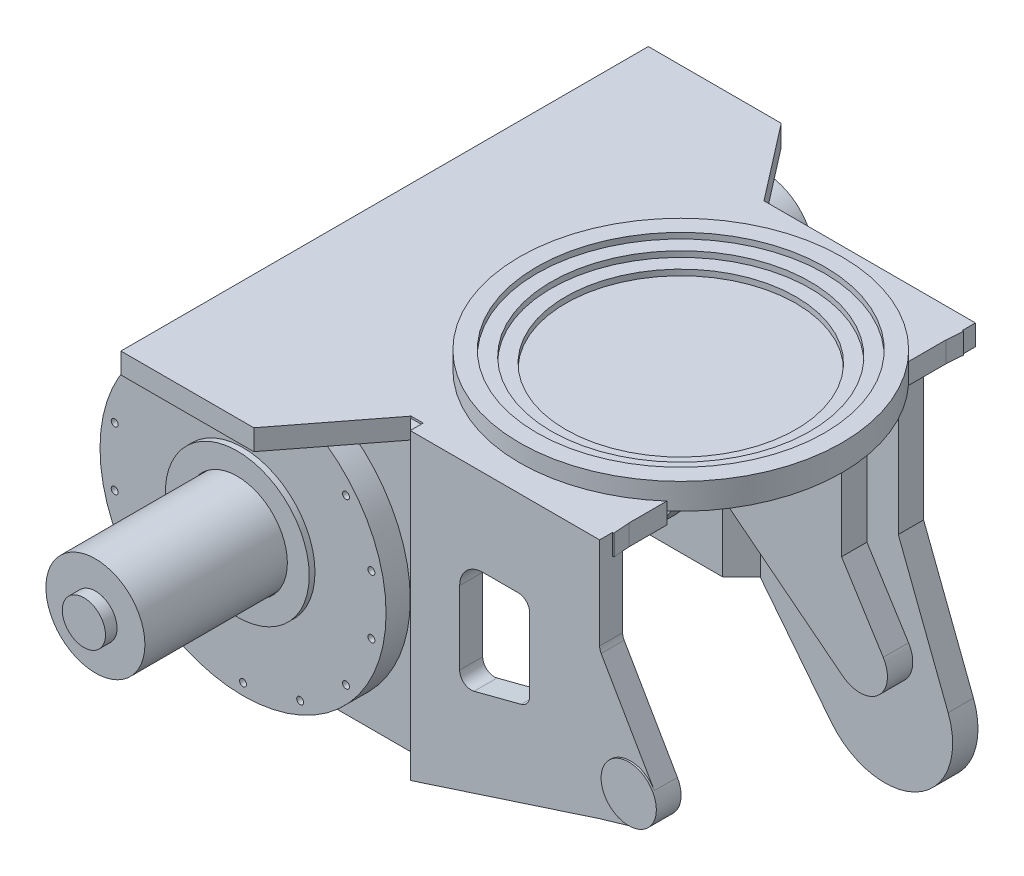
SolidWorks part; units mm, degrees
ref_plane "Front Plane" through (0, 0, 0) normal (0, 0, 1) x (1, 0, 0)
ref_plane "Top Plane" through (0, 0, 0) normal (0, 1, 0) x (1, 0, 0)
ref_plane "Right Plane" through (0, 0, 0) normal (1, 0, 0) x (0, 0, -1)
sketch "Sketch2" plane through (0, 0, 0) normal (0, 1, 0) x (1, 0, 0)
  line L1 (350, -275) -> (-350, -275)
  line L2 (350, -275) -> (350, 275)
  line L3 (350, 275) -> (-350, 275)
  line L4 (-350, -275) -> (-350, 275)
  line L5 (350, -275) -> (-350, 275) construction
  line L6 (350, 275) -> (-350, -275) construction
  point P0 (0, 0)
  dimension "D1" = 550
  dimension "D2" = 700
extrude "Boss-Extrude1" add sketch "Sketch2" along normal blind 2
sketch "Sketch3" plane through (0, 2, 0) normal (0, 1, 0) x (1, 0, 0)
  circle A0 centre (164.5242, 0) radius 280
  dimension "D1" = 560
extrude "Boss-Extrude3" add sketch "Sketch3" along normal blind 30 and the other way blind 15
sketch "Sketch7" plane through (0, 32, 0) normal (0, 1, 0) x (1, 0, 0)
  circle A0 centre (164.5242, 0) radius 250
extrude "Cut-Extrude2" cut sketch "Sketch7" against normal blind 10
sketch "Sketch9" plane through (0, 22, 0) normal (0, 1, 0) x (1, 0, 0)
  circle A0 centre (164.5242, 0) radius 225
extrude "Cut-Extrude3" cut sketch "Sketch9" against normal blind 10
sketch "Sketch10" plane through (0, 12, 0) normal (0, 1, 0) x (1, 0, 0)
  circle A0 centre (164.5242, 0) radius 200
extrude "Cut-Extrude4" cut sketch "Sketch10" against normal blind 10
sketch "Sketch12" plane through (0, 0, 0) normal (0, -1, 0) x (1, 0, 0)
  line L0 (-350, -275) -> (-350, -458.1483)
  line L1 (-350, -458.1483) -> (-119.077, -458.1483)
  line L2 (-119.077, -458.1483) -> (0, -303.9607)
  line L3 (352.1511, -303.9607) -> (0, -303.9607)
  line L4 (352.1511, -303.9607) -> (350, -275)
  line L5 (350, -275) -> (-350, -275)
  line L6 (-350, 275) -> (-350, 326.4525)
  line L7 (-350, 326.4525) -> (350, 326.4525)
  line L8 (350, 326.4525) -> (350, 275)
  line L9 (350, 275) -> (-350, 275)
extrude "Boss-Extrude7" add sketch "Sketch12" against normal blind 2
sketch "Sketch14" plane through (0, 2, 0) normal (0, 1, 0) x (1, 0, 0)
  line L0 (-350, 458.1483) -> (-350, -326.4525) construction
  line L1 (350, -326.4525) -> (-150, -326.4525)
  line L2 (350, -326.4525) -> (350, -286.4525)
  line L3 (350, -286.4525) -> (-150, -286.4525)
  line L4 (-150, -326.4525) -> (-150, -286.4525)
  dimension "D1" = 200
  dimension "D2" = 40
extrude "Boss-Extrude8" add sketch "Sketch14" against normal blind 582
sketch "Sketch16" plane through (0, 0, 326.4525) normal (0, 0, 1) x (1, 0, 0)
  line L0 (-150, -580) -> (350, -417.5402)
  line L1 (350, 2) -> (350, -580) construction
  line L2 (350, -417.5402) -> (350, -580)
  line L3 (350, -580) -> (-150, -580)
  line L4 (-150, -580) -> (-150, 0) construction
  dimension "D1" = 72
extrude "Cut-Extrude5" cut sketch "Sketch16" against normal blind 582
sketch "Sketch17" plane through (0, 0, 326.4525) normal (0, 0, 1) x (1, 0, 0)
  circle A0 centre (350, -417.5402) radius 5
sketch "Sketch19" plane through (0, 0, 326.4525) normal (0, 0, 1) x (1, 0, 0)
  line L1 (350, 2) -> (350, -417.5402) construction
  line L2 (350, -163) -> (475.6516, -380.635)
  line L3 (350, -417.5402) -> (475.6516, -380.635)
  line L4 (350, -417.5402) -> (350, -163)
extrude "Boss-Extrude9" add sketch "Sketch19" against normal up to surface (40 mm away) up to face at (100, -249.385, 286.4525)
sketch "Sketch20" plane through (0, 0, 326.4525) normal (0, 0, 1) x (1, 0, 0)
  line L0 (-150, -580) -> (21, -524.4387)
  line L1 (350, -417.5402) -> (-150, -580) construction
  line L2 (21, -524.4387) -> (21, 2)
  line L3 (350, 2) -> (-350, 2) construction
  line L5 (-150, 0) -> (-150, -580)
  line L8 (350, 2) -> (350, -163) construction
  line L9 (21, 2) -> (21, 86.1242)
  line L10 (21, 86.1242) -> (-150, 86.1242)
  line L11 (-150, 86.1242) -> (-150, 0)
  dimension "D1" = 329
extrude "Cut-Extrude9" cut sketch "Sketch20" against normal blind 40
sketch "Sketch21" plane through (0, 0, 326.4525) normal (0, 0, 1) x (1, 0, 0)
  line L0 (475.6516, -380.635) -> (350, -163) construction
  line L1 (350, -417.5402) -> (475.6516, -380.635) construction
  circle A0 centre (403.5663, -351.7796) radius 48
  dimension "D1" = 96
extrude "Boss-Extrude10" add sketch "Sketch21" along normal blind 3 and the other way up to surface (40 mm away) other way up to face at (261.2753, -247.6023, 286.4525)
sketch "Sketch22" plane through (0, 0, 326.4525) normal (0, 0, 1) x (1, 0, 0)
  line L2 (417.0931, -397.8342) -> (475.6516, -380.635)
  line L3 (475.6516, -380.635) -> (445.1356, -327.7796)
  line L4 (417.0931, -397.8342) -> (475.6516, -380.635)
  line L5 (475.6516, -380.635) -> (445.1356, -327.7796)
  arc A1 (417.0931, -397.8342) -> (445.1356, -327.7796) centre (403.5663, -351.7796) ccw
  arc A2 (417.0931, -397.8342) -> (445.1356, -327.7796) centre (403.5663, -351.7796) ccw
  dimension "D1" = 0
extrude "Cut-Extrude10" cut sketch "Sketch22" against normal blind 83
ref_plane "Plane2" through (0, -524.44, 0) normal (0, -1, 0) x (-1, 0, 0)
sketch "Sketch24" plane through (0, -524.44, 0) normal (0, -1, 0) x (-1, 0, 0)
  line L0 (-21, -286.4525) -> (14.3553, -251.0972)
  line L1 (14.3553, -251.0972) -> (431.5305, -251.0972)
  line L5 (-21, -326.4525) -> (-21, -286.4525)
  line L6 (-21, -326.4525) -> (22.5103, -282.9422)
  line L9 (22.5103, -282.9422) -> (431.5305, -282.9422)
  line L10 (150, -326.4525) -> (350, -326.4525) construction
  line L13 (431.5305, -282.9422) -> (431.5305, -251.0972)
  dimension "D1" = 50
  dimension "D2" = 135
extrude "Boss-Extrude13" add sketch "Sketch24" against normal blind 523
sketch "Sketch25" plane through (0, 0, 0) normal (0, -1, 0) x (1, 0, 0)
  line L1 (-150, 286.4525) -> (-350, 286.4525)
  line L2 (-150, 286.4525) -> (-150, 326.4525)
  line L3 (-150, 326.4525) -> (-350, 326.4525)
  line L4 (-350, 286.4525) -> (-350, 326.4525)
extrude "Cut-Extrude11" cut sketch "Sketch25" against normal blind 523
sketch "Sketch27" plane through (0, 0, 282.9422) normal (0, 0, 1) x (1, 0, 0)
  line L0 (-22.5103, -1.44) -> (-22.5103, -524.44) construction
  line L1 (-22.5103, -1.44) -> (-22.5103, -295.44)
  circle A0 centre (-271.0103, -295.44) radius 248.5
  line M2 (-431.5305, -524.44) -> (-22.5103, -524.44)
  line M5 (-431.5305, -1.44) -> (-431.5305, -524.44)
  dimension "D1" = 497
  dimension "D2" = 294
extrude "Boss-Extrude14" add sketch "Sketch27" against normal blind 73.85 and the other way blind 42 contours A0 M5 M2 | A0 M5 | A0 M2 region at (-243.9679, -291.8807, 282.9422) region at (-467.3178, -295.44, 282.9422) region at (-271.0103, -532.2668, 282.9422)
sketch "Sketch30" plane through (0, 0, 209.0922) normal (0, 0, -1) x (-1, 0, 0)
  circle A0 centre (271.0103, -295.44) radius 236.5
extrude "Boss-Extrude15" add sketch "Sketch30" along normal blind 16
sketch "Sketch31" plane through (0, 0, 193.0922) normal (0, 0, -1) x (-1, 0, 0)
  circle A0 centre (271.0103, -295.44) radius 197.5
extrude "Boss-Extrude16" add sketch "Sketch31" along normal blind 15
sketch "Sketch32" plane through (0, 0, 178.0922) normal (0, 0, -1) x (-1, 0, 0)
  circle A0 centre (271.0103, -295.44) radius 162.5
extrude "Boss-Extrude17" add sketch "Sketch32" along normal blind 7
sketch "Sketch33" plane through (0, 0, 171.0922) normal (0, 0, -1) x (-1, 0, 0)
  circle A0 centre (271.0103, -295.44) radius 137.5
extrude "Boss-Extrude18" add sketch "Sketch33" along normal blind 12
sketch "Sketch34" plane through (0, 0, 324.9422) normal (0, 0, 1) x (1, 0, 0)
  circle A0 centre (-271.0103, -295.44) radius 125
extrude "Boss-Extrude19" add sketch "Sketch34" along normal blind 10
sketch "Sketch35" plane through (0, 0, 334.9422) normal (0, 0, 1) x (1, 0, 0)
  circle A0 centre (-271.0103, -295.44) radius 87
extrude "Cut-Extrude12" cut sketch "Sketch35" against normal blind 50
sketch "Sketch36" plane through (0, 0, 284.9422) normal (0, 0, 1) x (1, 0, 0)
  circle A0 centre (-271.0103, -295.44) radius 86
extrude "Boss-Extrude20" add sketch "Sketch36" along normal blind 296.5
sketch "Sketch37" plane through (0, 0, 581.4422) normal (0, 0, 1) x (1, 0, 0)
  circle A0 centre (-271.0103, -295.44) radius 37.5
extrude "Boss-Extrude21" add sketch "Sketch37" along normal blind 20
fillet "Fillet1" radius 20 1 edges at (350, -163, 306.4525)
mirror "Mirror4" about plane through (0, 0, 0) normal (0, 0, 1) of "Boss-Extrude7", "Boss-Extrude10", "Boss-Extrude1", "Boss-Extrude9", "Cut-Extrude5", "Boss-Extrude8", "Boss-Extrude18", "Boss-Extrude17", "Boss-Extrude16", "Boss-Extrude15", "Boss-Extrude13", "Boss-Extrude14", "Boss-Extrude19", "Boss-Extrude21", "Boss-Extrude20"
sketch "Sketch40" plane through (0, 0, -286.4525) normal (0, 0, 1) x (1, 0, 0)
  line L12 (-150, 0) -> (-150, -78.3945)
  line L13 (-150, -512.4855) -> (-150, -580)
  line L14 (-150, -580) -> (20.9961, -524.44)
  line L15 (20.9961, -524.44) -> (-19, -524.44)
  line L16 (-19, -524.44) -> (-19, -1.44)
  line L17 (-19, -1.44) -> (21, -1.44)
  line L18 (21, -1.44) -> (21, -524.4387)
  line L19 (21, -524.4387) -> (350, -417.5402)
  line L20 (350, -417.5402) -> (475.6516, -380.635)
  line L21 (475.6516, -380.635) -> (350, -163)
  line L22 (350, -163) -> (350, 0)
  line L23 (350, 0) -> (-150, 0)
  line L24 (-150, 0) -> (-150, -78.3945)
  line L25 (-150, -512.4855) -> (-150, -580)
  line L26 (-150, -580) -> (20.9961, -524.44)
  line L27 (20.9961, -524.44) -> (-19, -524.44)
  line L28 (-19, -524.44) -> (-19, -1.44)
  line L29 (-19, -1.44) -> (21, -1.44)
  line L30 (21, -1.44) -> (21, -524.4387)
  line L31 (21, -524.4387) -> (350, -417.5402)
  line L32 (350, -417.5402) -> (475.6516, -380.635)
  line L33 (475.6516, -380.635) -> (350, -163)
  line L34 (350, -163) -> (350, 0)
  line L35 (350, 0) -> (-150, 0)
  arc A1 (-150, -512.4855) -> (-150, -78.3945) centre (-271.0103, -295.44) ccw
  arc A2 (-150, -512.4855) -> (-150, -78.3945) centre (-271.0103, -295.44) ccw
  dimension "D1" = 0
extrude "Cut-Extrude14" cut sketch "Sketch40" against normal blind 80
sketch "Sketch41" plane through (0, 0, -326.4525) normal (0, 0, -1) x (-1, 0, 0)
  line L0 (-21, -524.44) -> (-119.3307, -649.1719)
  line L2 (-338.0133, -541.9318) -> (-260, -339.44)
  line L3 (-260, -339.44) -> (-260, 2)
  line L4 (-350, 2) -> (17.3701, 2) construction
  line L5 (-260, 2) -> (-21, -1.44)
  line L6 (-21, -1.44) -> (-21, -524.44)
  line L7 (-21, -524.44) -> (-479.957, -524.44) construction
  line L8 (-119.3307, -649.1719) -> (-143.4961, -679.8256)
  line L9 (-338.0133, -541.9318) -> (-346.5828, -564.1748)
  arc A0 (-346.5828, -564.1748) -> (-143.4961, -679.8256) centre (-236.3045, -606.6613) ccw
  dimension "D1" = 239
  dimension "D2" = 158.83
  dimension "D3" = 217
  dimension "D4" = 158.93
  dimension "D5" = 141.75
  dimension "D6" = 185
extrude "Boss-Extrude22" add sketch "Sketch41" against normal blind 44
sketch "Sketch42" plane through (0, 0, -326.4525) normal (0, 0, -1) x (-1, 0, 0)
  circle A0 centre (-236.3045, -606.6613) radius 84
extrude "Boss-Extrude23" add sketch "Sketch42" along normal blind 5
sketch "Sketch43" plane through (0, 0, -331.4525) normal (0, 0, -1) x (-1, 0, 0)
  circle A0 centre (-236.3045, -606.6613) radius 56
extrude "Boss-Extrude24" add sketch "Sketch43" along normal blind 9
sketch "Sketch44" plane through (0, 0, -340.4525) normal (0, 0, -1) x (-1, 0, 0)
  circle A0 centre (-236.3045, -606.6613) radius 31
extrude "Boss-Extrude25" add sketch "Sketch44" along normal blind 12
sketch "Sketch45" plane through (0, 0, -352.4525) normal (0, 0, -1) x (-1, 0, 0)
  circle A0 centre (-236.3045, -606.6613) radius 27
extrude "Boss-Extrude26" add sketch "Sketch45" along normal blind 4
sketch "Sketch46" plane through (0, 0, -282.9422) normal (0, 0, -1) x (-1, 0, 0)
  line L0 (349.8838, -1.44) -> (431.5305, -102.5155)
  line L1 (22.5103, -1.44) -> (431.5305, -1.44) construction
  line L2 (431.5305, -1.44) -> (431.5305, -105.7415) construction
  line L3 (431.5305, -102.5155) -> (431.5305, -1.44)
  line L4 (431.5305, -1.44) -> (349.8838, -1.44)
extrude "Cut-Extrude18" cut sketch "Sketch46" against normal through all contours L4 L0 L3
sketch "Sketch50" plane through (-211.0253, 170.4617, 0) normal (-0.7779, 0.6284, 0) x (0, 0, 1)
  line L0 (282.9422, -350.9118) -> (-282.9422, -350.9118)
  line L1 (282.9422, -350.9118) -> (251.0972, -350.9118) construction
  line L2 (-282.9422, -350.9118) -> (-282.9422, -220.9794)
  line L3 (-282.9422, -220.9794) -> (282.9422, -220.9794)
  line L4 (282.9422, -220.9794) -> (282.9422, -350.9118)
extrude "Boss-Extrude28" add sketch "Sketch50" against normal blind 5
sketch "Sketch51" plane through (-211.0253, 170.4617, 0) normal (-0.7779, 0.6284, 0) x (0, 0, 1)
  line L0 (-251.0972, -350.9118) -> (251.0972, -350.9118) construction
  line L1 (122.2502, -350.9118) -> (42.4318, -350.9118)
  line L2 (122.2502, -350.9118) -> (122.2502, -302.3775)
  line L3 (122.2502, -302.3775) -> (42.4318, -302.3775)
  line L4 (42.4318, -350.9118) -> (42.4318, -302.3775)
extrude "Cut-Extrude19" cut sketch "Sketch51" against normal blind 5
sketch "Sketch52" plane through (-211.0253, 170.4617, 0) normal (-0.7779, 0.6284, 0) x (0, 0, 1)
  line L0 (-251.0972, -350.9118) -> (42.4318, -350.9118) construction
  line L1 (-127.4075, -350.9118) -> (-55.046, -350.9118)
  line L2 (-127.4075, -350.9118) -> (-127.4075, -302.3775)
  line L3 (-127.4075, -302.3775) -> (-55.046, -302.3775)
  line L4 (-55.046, -350.9118) -> (-55.046, -302.3775)
extrude "Cut-Extrude20" cut sketch "Sketch52" against normal blind 5
ref_plane "Plane3" through (0, 0, -116.4525) normal (0, 0, -1) x (-1, 0, 0)
sketch "Sketch55" plane through (0, 0, -116.4525) normal (0, 0, -1) x (-1, 0, 0)
  line L0 (-373.5582, -390.624) -> (-140.9519, -208.2316)
  line L1 (-443.8156, -327.3083) -> (-371.443, -212.1641)
  line L5 (-61.443, -93) -> (-140.9519, -208.2316)
  line L6 (-371.443, -212.1641) -> (-371.443, -13)
  line L7 (-444.5242, -13) -> (115.4758, -13) construction
  line L8 (-371.443, -13) -> (-61.443, -13)
  line L9 (-61.443, -13) -> (-61.443, -93)
  arc A0 (-443.8156, -327.3083) -> (-373.5582, -390.624) centre (-403.1765, -352.8516) ccw
  dimension "D1" = 310
  dimension "D2" = 80
  dimension "D3" = 199.1641
  dimension "D4" = 140
extrude "Boss-Extrude29" add sketch "Sketch55" against normal blind 44
sketch "Sketch57" plane through (0, 0, 326.4525) normal (0, 0, 1) x (1, 0, 0)
  line L0 (208.482, -148.32) -> (146.8301, -148.32)
  line L1 (106.8301, -188.32) -> (106.8301, -315.4783)
  line L2 (131.8586, -334.8359) -> (213.5105, -313.6251)
  line L3 (228.482, -294.2676) -> (228.482, -168.32)
  arc A0 (146.8301, -148.32) -> (106.8301, -188.32) centre (146.8301, -188.32) ccw
  arc A1 (208.482, -148.32) -> (228.482, -168.32) centre (208.482, -168.32) cw
  arc A2 (213.5105, -313.6251) -> (228.482, -294.2676) centre (208.482, -294.2676) ccw
  arc A3 (106.8301, -315.4783) -> (131.8586, -334.8359) centre (126.8301, -315.4783) ccw
  dimension "D1" = 40
  dimension "D2" = 20
extrude "Cut-Extrude21" cut sketch "Sketch57" against normal blind 84
sketch "Sketch58" plane through (0, 0, -326.4525) normal (0, 0, -1) x (-1, 0, 0)
  line L0 (-157.0738, -257.6457) -> (-37.7461, -163.6967)
  line L1 (-29.3553, -146.4112) -> (-29.3553, -68.0328)
  line L2 (-51.3553, -46.0328) -> (-162.2533, -46.0328)
  line L3 (-184.2533, -68.0328) -> (-184.2533, -262.0746)
  line L4 (-182.2533, -264.0746) -> (-175.6318, -264.0746)
  arc A0 (-157.0738, -257.6457) -> (-175.6318, -264.0746) centre (-175.6318, -234.0746) cw
  arc A1 (-184.2533, -262.0746) -> (-182.2533, -264.0746) centre (-182.2533, -262.0746) ccw
  arc A2 (-162.2533, -46.0328) -> (-184.2533, -68.0328) centre (-162.2533, -68.0328) ccw
  arc A3 (-29.3553, -68.0328) -> (-51.3553, -46.0328) centre (-51.3553, -68.0328) ccw
  arc A4 (-37.7461, -163.6967) -> (-29.3553, -146.4112) centre (-51.3553, -146.4112) ccw
  dimension "D1" = 30
  dimension "D2" = 2
  dimension "D3" = 22
extrude "Cut-Extrude22" cut sketch "Sketch58" against normal blind 84
sketch "Sketch59" plane through (0, 0, 0) normal (0, -1, 0) x (1, 0, 0)
  line L0 (-119.077, -458.1483) -> (-68.2236, -392.3004)
  line L1 (-119.077, -458.1483) -> (-17.3701, -326.4525) construction
  line L23 (121.0465, -282.4525) -> (260, -282.4525)
  line L24 (260, -282.4525) -> (260, -326.4525)
  line L25 (260, -326.4525) -> (350, -326.4525)
  line L26 (350, -326.4525) -> (350, -303.9607)
  line L27 (350, -303.9607) -> (352.1511, -303.9607)
  line L28 (352.1511, -303.9607) -> (350, -275)
  line L29 (350, -275) -> (350, -209.7587)
  line L30 (350, 209.7587) -> (350, 275)
  line L31 (350, 275) -> (352.1511, 303.9607)
  line L32 (352.1511, 303.9607) -> (350, 303.9607)
  line L33 (350, 303.9607) -> (350, 286.4525)
  line L34 (350, 286.4525) -> (21, 286.4525)
  line L35 (21, 286.4525) -> (21, 303.9607)
  line L36 (21, 303.9607) -> (0, 303.9607)
  line L37 (0, 303.9607) -> (-119.077, 458.1483)
  line L38 (-119.077, 458.1483) -> (-350, 458.1483)
  line L39 (-350, 458.1483) -> (-350, -458.1483)
  line L40 (-350, -458.1483) -> (-119.077, -458.1483)
  line L41 (-119.077, -458.1483) -> (-17.3701, -326.4525)
  line L42 (-17.3701, -326.4525) -> (121.0465, -326.4525)
  line L43 (121.0465, -326.4525) -> (121.0465, -282.4525)
  line L44 (121.0465, -282.4525) -> (260, -282.4525)
  line L45 (260, -282.4525) -> (260, -326.4525)
  line L46 (260, -326.4525) -> (350, -326.4525)
  line L47 (350, -326.4525) -> (350, -303.9607)
  line L48 (350, -303.9607) -> (352.1511, -303.9607)
  line L49 (352.1511, -303.9607) -> (350, -275)
  line L50 (350, -275) -> (350, -209.7587)
  line L51 (350, 209.7587) -> (350, 275)
  line L52 (350, 275) -> (352.1511, 303.9607)
  line L53 (352.1511, 303.9607) -> (350, 303.9607)
  line L54 (350, 303.9607) -> (350, 286.4525)
  line L55 (350, 286.4525) -> (21, 286.4525)
  line L56 (21, 286.4525) -> (21, 303.9607)
  line L57 (21, 303.9607) -> (0, 303.9607)
  line L58 (0, 303.9607) -> (-119.077, 458.1483)
  line L59 (-119.077, 458.1483) -> (-350, 458.1483)
  line L60 (-350, 458.1483) -> (-350, -458.1483)
  line L61 (-350, -458.1483) -> (-119.077, -458.1483)
  line L62 (-68.2236, -392.3004) -> (-17.3701, -326.4525)
  line L63 (-17.3701, -326.4525) -> (121.0465, -326.4525)
  line L64 (121.0465, -326.4525) -> (121.0465, -282.4525)
  arc A1 (350, 209.7587) -> (350, -209.7587) centre (164.5242, 0) ccw
  arc A2 (350, 209.7587) -> (350, -209.7587) centre (164.5242, 0) ccw
  dimension "D1" = 0
extrude "Boss-Extrude30" add sketch "Sketch59" along normal blind 34
sketch "Sketch60" plane through (0, 0, 324.9422) normal (0, 0, 1) x (1, 0, 0)
  line L0 (-271.0103, -295.44) -> (-271.0103, -944.4608) construction
  circle A0 centre (-271.0103, -524.1748) radius 6
  circle A1 centre (-370.2546, -501.5229) radius 6
  circle A2 centre (-449.8423, -438.0538) radius 6
  circle A3 centre (-494.0102, -346.3383) radius 6
  circle A4 centre (-494.0102, -244.5417) radius 6
  circle A5 centre (-449.8423, -152.8262) radius 6
  circle A6 centre (-370.2546, -89.3571) radius 6
  circle A7 centre (-271.0103, -66.7052) radius 6
  circle A8 centre (-171.766, -89.3571) radius 6
  circle A9 centre (-92.1783, -152.8262) radius 6
  circle A10 centre (-48.0104, -244.5417) radius 6
  circle A11 centre (-48.0104, -346.3383) radius 6
  circle A12 centre (-92.1783, -438.0538) radius 6
  circle A13 centre (-171.766, -501.5229) radius 6
  point P33 (-271.0103, -295.44)
  dimension "D1" = 12
  dimension "D2" = 14
extrude "Cut-Extrude23" cut sketch "Sketch60" against normal blind 10
sketch "Sketch61" plane through (0, 0, -324.9422) normal (0, 0, -1) x (-1, 0, 0)
  circle A0 centre (271.0103, -295.44) radius 248.5
extrude "Boss-Extrude31" add sketch "Sketch61" along normal blind 2
sketch "Sketch62" plane through (0, 0, -326.9422) normal (0, 0, -1) x (-1, 0, 0)
  line L0 (271.0103, -295.44) -> (271.0103, -625.1669) construction
  circle A2 centre (271.0103, -515.44) radius 6
  circle A3 centre (175.5559, -493.6532) radius 6
  circle A4 centre (99.0074, -432.6078) radius 6
  circle A5 centre (56.5262, -344.3946) radius 6
  circle A6 centre (56.5262, -246.4854) radius 6
  circle A7 centre (99.0074, -158.2722) radius 6
  circle A8 centre (175.5559, -97.2268) radius 6
  circle A9 centre (271.0103, -75.44) radius 6
  circle A10 centre (366.4647, -97.2268) radius 6
  circle A11 centre (443.0132, -158.2722) radius 6
  circle A12 centre (485.4944, -246.4854) radius 6
  circle A13 centre (485.4944, -344.3946) radius 6
  circle A14 centre (443.0132, -432.6078) radius 6
  circle A15 centre (366.4647, -493.6532) radius 6
  point P34 (271.0103, -295.44)
  dimension "D1" = 14
  dimension "D2" = 220
extrude "Cut-Extrude24" cut sketch "Sketch62" against normal blind 1
